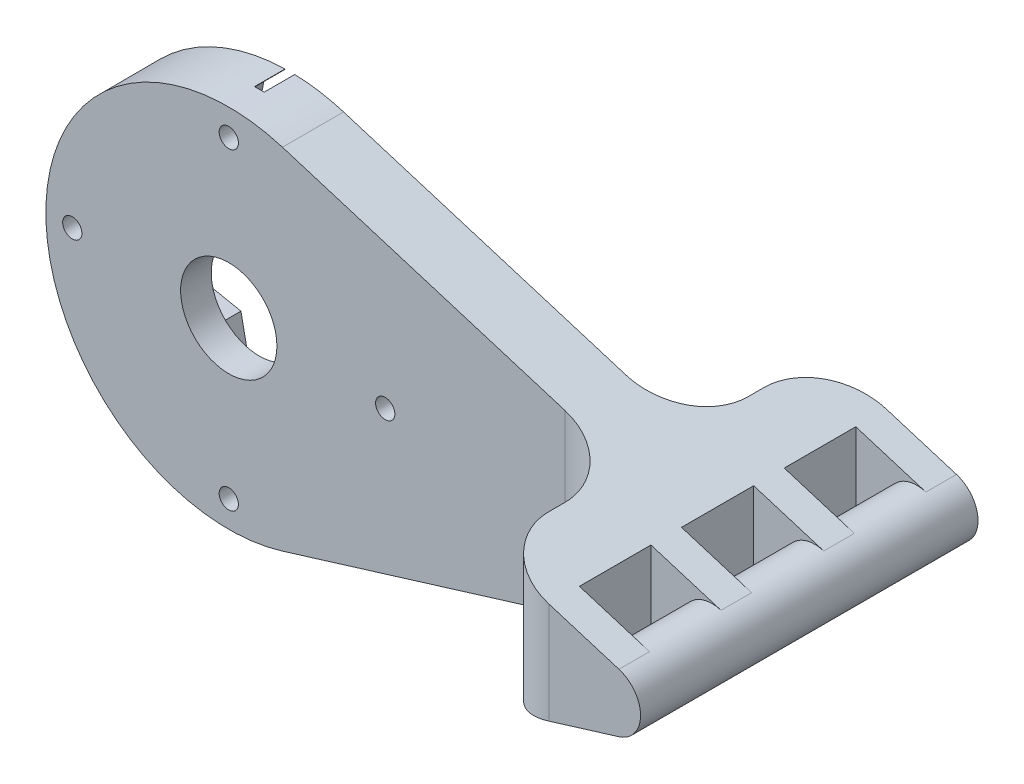
SolidWorks part; units mm, degrees
ref_plane "Front Plane" through (0, 0, 0) normal (0, 0, 1) x (1, 0, 0)
ref_plane "Top Plane" through (0, 0, 0) normal (0, 1, 0) x (1, 0, 0)
ref_plane "Right Plane" through (0, 0, 0) normal (1, 0, 0) x (0, 0, -1)
sketch "Sketch1" plane through (0, 0, 0) normal (0, 0, 1) x (1, 0, 0)
  line L7 (146.05, 3.175) -> (146.05, 4.063)
  line L8 (0, 0) -> (279.4, 0)
  line L9 (0, 0) -> (0, 3.175)
  line L10 (0, 3.175) -> (279.4, 3.175)
  line L11 (279.4, 0) -> (279.4, 3.175)
  line L12 (260.35, 3.175) -> (215.9, 3.175)
  line L13 (260.35, 3.175) -> (260.35, 91.44) construction
  line L14 (254, 97.79) -> (222.25, 97.79)
  line L15 (215.9, 3.175) -> (215.9, 91.44) construction
  line L16 (260.35, 91.44) -> (279.4, 3.175)
  line L17 (165.0718, 64.0362) -> (215.9, 13.208) construction
  line L18 (170.5184, 69.8101) -> (222.7846, 20.5062)
  line L19 (215.9, 91.44) -> (215.9, 89.5783)
  line L20 (0, 19.05) -> (0, 30.1625)
  line L21 (3.175, 19.05) -> (3.175, 30.1625)
  line L22 (3.175, 30.1625) -> (0, 30.1625) construction
  line L23 (26.8735, 12.7) -> (70.8676, 19.05)
  line L24 (238.125, 97.79) -> (238.125, 3.175) construction
  line L25 (165.0718, 64.0362) -> (292.0718, 64.0362) construction
  line L26 (238.125, 76.7362) -> (292.0718, 67.2112)
  line L27 (238.125, 51.3362) -> (292.0718, 60.8612)
  arc A6 (260.35, 91.44) -> (254, 97.79) centre (254, 91.44) ccw
  arc A7 (222.25, 97.79) -> (215.9, 91.44) centre (222.25, 91.44) ccw
  circle A9 centre (215.9, 13.208) radius 3.175
  arc A10 (216.7962, 82.0441) -> (216.9572, 88.0838) centre (215.9, 85.09) ccw
  arc A11 (154.4343, 15.0798) -> (215.6899, 80.8367) centre (131.5684, 97.79) ccw
  arc A12 (146.05, 4.063) -> (154.4343, 15.0798) centre (157.48, 4.063) cw
  circle A13 centre (215.9, 13.208) radius 10.033
  circle A14 centre (165.0718, 64.0362) radius 3.175
  circle A15 centre (165.0718, 64.0362) radius 7.9375
  arc A16 (0, 19.05) -> (15.875, 3.175) centre (15.875, 19.05) ccw
  arc A17 (3.175, 19.05) -> (26.8735, 12.7) centre (15.875, 19.05) ccw
  circle A18 centre (15.875, 19.05) radius 15.875 construction
  circle A19 centre (15.875, 19.05) radius 12.7 construction
  arc A20 (70.8676, 19.05) -> (158.9067, 69.0358) centre (51.0253, 156.5215) ccw
  arc A21 (215.6899, 80.8367) -> (216.7962, 82.0441) centre (217.2436, 80.5236) cw
  arc A22 (215.9, 89.5783) -> (216.9572, 88.0838) centre (217.485, 89.5783) ccw
  arc A23 (3.175, 30.1625) -> (0, 30.1625) centre (1.5875, 30.1625) ccw
  circle A24 centre (238.125, 64.0362) radius 12.7
  circle A25 centre (292.0718, 64.0362) radius 3.175
  point P11 (260.35, 97.79)
  point P14 (215.9, 97.79)
  point P27 (146.05, 13.208)
  point P48 (215.9, 81.915)
  point P51 (215.9, 88.265)
  dimension "D4" = 97.79
  dimension "D6" = 6.35
  dimension "D8" = 6.35
  dimension "D7" = 6.35
  dimension "D10" = 12.7
  dimension "D12" = 11.43
  dimension "D13" = 6.35
  dimension "D16" = 15.875
  dimension "D18" = 31.75
  dimension "D24" = 1.585
  dimension "D26" = 25.4
  dimension "D27" = 6.35
  dimension "D1" = 3.175
  dimension "D2" = 279.4
  dimension "D3" = 44.45
  dimension "D5" = 19.05
  dimension "D9" = 71.882
  dimension "D11" = 114.3
  dimension "D14" = 71.882
  dimension "D15" = 45
  dimension "D17" = 200.025
  dimension "D19" = 30.1625
  dimension "D21" = 12.7
  dimension "D22" = 44.45
  dimension "D23" = 19.05
  dimension "D25" = 127
  dimension "D20" = 3.175
ref_plane "Plane2" through (0, 0, 17.526) normal (0, 0, 1) x (1, 0, 0)
ref_plane "Plane3" through (0, 0, 34.925) normal (0, 0, 1) x (1, 0, 0)
ref_plane "Plane4" through (0, 0, 22.2885) normal (0, 0, 1) x (1, 0, 0)
sketch "Sketch3" plane through (0, 0, 0) normal (0, 0, 1) x (1, 0, 0)
  line L0 (293.0031, 67.0716) -> (243.6986, 82.2004)
  line L1 (243.6986, 45.8721) -> (293.0031, 61.0009)
  arc A0 (243.6986, 82.2004) -> (243.6986, 45.8721) centre (238.125, 64.0362) ccw
  circle A1 centre (238.125, 64.0362) radius 16.25 construction
  circle A2 centre (238.125, 80.2862) radius 1
  circle A3 centre (254.375, 64.0362) radius 1
  circle A4 centre (221.875, 64.0362) radius 1
  circle A5 centre (238.125, 47.7862) radius 1
  arc A6 (293.0031, 61.0009) -> (293.0031, 67.0716) centre (292.0718, 64.0362) ccw
  point P0 (238.125, 64.0362)
  point P2 (292.0718, 64.0362)
  dimension "D1" = 38
  dimension "D2" = 32.5
  dimension "D3" = 2
  dimension "D4" = 6.35
extrude "Boss-Extrude1" add sketch "Sketch3" along normal blind 3.175
sketch "Sketch4" plane through (0, 0, 0) normal (0, 0, -1) x (-1, 0, 0)
  line L0 (-254.925, 66.7307) -> (-239.325, 69.915)
  line L1 (-254.925, 61.3418) -> (-239.325, 58.1575)
  line L2 (-240.8194, 47.2362) -> (-244.0038, 62.8362)
  line L3 (-240.8194, 80.8362) -> (-244.0038, 65.2362)
  line L4 (-235.4306, 80.8362) -> (-232.2462, 65.2362)
  line L5 (-236.925, 69.915) -> (-221.325, 66.7307)
  line L6 (-235.4306, 47.2362) -> (-232.2462, 62.8362)
  line L7 (-236.925, 58.1575) -> (-221.325, 61.3418)
  line L9 (-238.625, 82.5362) -> (-237.625, 82.5362)
  line L10 (-293.0031, 61.0009) -> (-243.6986, 45.8721)
  line L11 (-243.6986, 82.2004) -> (-293.0031, 67.0716)
  line L12 (-293.0031, 61.0009) -> (-243.6986, 45.8721)
  line L13 (-243.6986, 82.2004) -> (-293.0031, 67.0716)
  line L14 (-238.625, 82.5362) -> (-238.625, 83.5362)
  line L15 (-238.625, 83.5362) -> (-237.625, 83.5362)
  line L16 (-237.625, 82.5362) -> (-237.625, 83.5362)
  line L17 (-238.625, 82.5362) -> (-237.625, 83.5362) construction
  line L18 (-238.625, 83.5362) -> (-237.625, 82.5362) construction
  line L19 (-238.625, 44.5362) -> (-237.625, 44.5362)
  line L20 (-238.625, 44.5362) -> (-238.625, 45.5362)
  line L21 (-238.625, 45.5362) -> (-237.625, 45.5362)
  line L22 (-237.625, 44.5362) -> (-237.625, 45.5362)
  line L23 (-238.625, 44.5362) -> (-237.625, 45.5362) construction
  line L24 (-238.625, 45.5362) -> (-237.625, 44.5362) construction
  line L25 (-219.625, 63.5362) -> (-218.625, 63.5362)
  line L26 (-219.625, 63.5362) -> (-219.625, 64.5362)
  line L27 (-219.625, 64.5362) -> (-218.625, 64.5362)
  line L28 (-218.625, 63.5362) -> (-218.625, 64.5362)
  line L29 (-219.625, 63.5362) -> (-218.625, 64.5362) construction
  line L30 (-219.625, 64.5362) -> (-218.625, 63.5362) construction
  circle A0 centre (-238.125, 64.0362) radius 6
  circle A1 centre (-238.125, 80.2862) radius 2.75
  circle A2 centre (-221.875, 64.0362) radius 2.75
  circle A3 centre (-238.125, 47.7862) radius 2.75
  circle A4 centre (-254.375, 64.0362) radius 2.75
  arc A5 (-243.6986, 45.8721) -> (-243.6986, 82.2004) centre (-238.125, 64.0362) ccw construction
  arc A6 (-243.6986, 45.8721) -> (-243.6986, 82.2004) centre (-238.125, 64.0362) ccw construction
  arc A9 (-293.0031, 67.0716) -> (-293.0031, 61.0009) centre (-292.0718, 64.0362) ccw
  arc A10 (-243.6986, 45.8721) -> (-243.6986, 82.2004) centre (-238.125, 64.0362) ccw
  arc A11 (-293.0031, 67.0716) -> (-293.0031, 61.0009) centre (-292.0718, 64.0362) ccw
  arc A12 (-243.6986, 45.8721) -> (-243.6986, 82.2004) centre (-238.125, 64.0362) ccw
  point P37 (-238.125, 83.0362)
  point P48 (-238.125, 45.0362)
  point P53 (-219.125, 64.0362)
  arc M17 (-293.0031, 67.0716) -> (-293.0031, 61.0009) centre (-292.0718, 64.0362) ccw
  line M18 (-293.0031, 61.0009) -> (-243.6986, 45.8721)
  arc M19 (-243.6986, 45.8721) -> (-243.6986, 82.2004) centre (-238.125, 64.0362) ccw
  line M20 (-243.6986, 82.2004) -> (-293.0031, 67.0716)
  dimension "D1" = 12
  dimension "D3" = 1
  dimension "D4" = 1
  dimension "D2" = 0
extrude "Boss-Extrude3" add sketch "Sketch4" along normal blind 3.175 contours A4 L0 L3 A1 A3 L2 L1 M19 M20 M17 M18 | A2 L27 L16 A1 L4 L5 M19 | A3 L22 L25 A2 L7 L6 M19 region at (262.9971, 64.0362, 0) region at (228.1389, 74.0223, 0) region at (228.1389, 54.0502, 0)
sketch "Sketch5" plane through (0, 0, 0) normal (0, 0, 1) x (1, 0, 0)
  line L0 (285.7218, 64.0362) -> (285.7218, 69.3058)
  line L1 (285.7218, 64.0362) -> (285.7218, 58.7667)
  line L2 (293.0031, 67.0716) -> (243.6986, 82.2004)
  line L3 (243.6986, 45.8721) -> (293.0031, 61.0009)
  line L4 (293.0031, 67.0716) -> (243.6986, 82.2004)
  line L5 (243.6986, 45.8721) -> (293.0031, 61.0009)
  line L6 (279.3718, 56.8182) -> (279.3718, 71.2543)
  circle A0 centre (292.0718, 64.0362) radius 3.175
  arc A1 (293.0031, 61.0009) -> (293.0031, 67.0716) centre (292.0718, 64.0362) ccw construction
  circle A2 centre (292.0718, 64.0362) radius 6.35
  arc A5 (293.0031, 61.0009) -> (293.0031, 67.0716) centre (292.0718, 64.0362) ccw
  arc A6 (243.6986, 82.2004) -> (243.6986, 45.8721) centre (238.125, 64.0362) ccw
  arc A7 (293.0031, 61.0009) -> (293.0031, 67.0716) centre (292.0718, 64.0362) ccw
  arc A8 (243.6986, 82.2004) -> (243.6986, 45.8721) centre (238.125, 64.0362) ccw
  point P19 (285.7218, 61.4015)
  dimension "D3" = 6.35
  dimension "D1" = 3.175
  dimension "D2" = 0
extrude "Boss-Extrude6" add sketch "Sketch5" along normal mid plane 35.052 contours L6 L5 L1 L0 L4 | A0 region at (282.3816, 64.0362, 0) region at (292.0718, 64.0362, 0)
sketch "Sketch6" plane through (0, 0, -17.526) normal (0, 0, -1) x (-1, 0, 0)
  line L0 (-279.3718, 56.8182) -> (-279.3718, 71.2543) construction
  line L1 (-279.3718, 71.2543) -> (-285.7218, 69.3058) construction
  line L2 (-285.7218, 69.3058) -> (-285.7218, 58.7667) construction
  line L3 (-285.7218, 58.7667) -> (-279.3718, 56.8182) construction
  line L4 (-279.3718, 56.8182) -> (-279.3718, 71.2543)
  line L5 (-279.3718, 71.2543) -> (-285.7218, 69.3058)
  line L6 (-285.7218, 69.3058) -> (-285.7218, 58.7667)
  line L7 (-285.7218, 58.7667) -> (-279.3718, 56.8182)
  line L8 (-285.7218, 58.7667) -> (-293.0031, 61.0009)
  line L9 (-293.0031, 67.0716) -> (-285.7218, 69.3058)
  circle A0 centre (-292.0718, 64.0362) radius 3.175 construction
  circle A1 centre (-292.0718, 64.0362) radius 3.175
  line M2 (-279.3718, 56.8182) -> (-279.3718, 71.2543)
  line M3 (-279.3718, 71.2543) -> (-285.7218, 69.3058)
  line M4 (-285.7218, 69.3058) -> (-285.7218, 58.7667)
  line M5 (-285.7218, 58.7667) -> (-279.3718, 56.8182)
extrude "Boss-Extrude7" add sketch "Sketch6" against normal blind 3.175 contours A1 L8 L9 M4 | A1 | M5 M2 M3 M4 region at (282.3816, 64.0362, -17.526) region at (287.8218, 64.0362, -17.526) region at (292.0718, 64.0362, -17.526)
sketch "Sketch7" plane through (0, 0, 3.175) normal (0, 0, 1) x (1, 0, 0)
  line L3 (285.7218, 58.7667) -> (293.0031, 61.0009)
  line L4 (293.0031, 67.0716) -> (285.7218, 69.3058)
  line L5 (285.7218, 69.3058) -> (285.7218, 58.7667)
  line L6 (285.7218, 58.7667) -> (293.0031, 61.0009)
  line L7 (293.0031, 67.0716) -> (285.7218, 69.3058)
  line L8 (285.7218, 69.3058) -> (285.7218, 58.7667)
  arc A1 (293.0031, 67.0716) -> (293.0031, 61.0009) centre (292.0718, 64.0362) ccw
  arc A2 (293.0031, 67.0716) -> (293.0031, 61.0009) centre (292.0718, 64.0362) ccw
  dimension "D1" = 0
extrude "Cut-Extrude1" cut sketch "Sketch7" against normal up to next
ref_plane "Plane5" through (0, 0, -5.334) normal (0, 0, 1) x (1, 0, 0)
extrude "Boss-Extrude8" add sketch "Sketch7<5>" along normal mid plane 3.175 from surface starting at plane "Plane5"
sketch "Sketch7<5>" plane through (0, 0, 3.175) normal (0, 0, 1) x (1, 0, 0) same geometry as "Sketch7"
mirror "Mirror3" about plane through (0, 0, 0) normal (0, 0, 1) of "Boss-Extrude7"
ref_plane "Plane6" through (0, 0, 5.334) normal (0, 0, -1) x (-1, 0, 0)
extrude "Boss-Extrude9" add sketch "Sketch7<6>" along normal mid plane 3.175 from surface starting at plane "Plane6"
sketch "Sketch7<6>" plane through (0, 0, 3.175) normal (0, 0, 1) x (1, 0, 0) same geometry as "Sketch7"
fillet "Fillet2" radius 6.35 4 edges at (279.3718, 64.0362, -17.526) (279.3718, 64.0362, -3.175) (279.3718, 64.0362, 17.526) (279.3718, 64.0362, 3.175)
sketch "Sketch8" plane through (0, 0, 3.175) normal (0, 0, 1) x (1, 0, 0)
  arc A0 (243.6986, 82.2004) -> (243.6986, 45.8721) centre (238.125, 64.0362) ccw construction
  arc A1 (243.6986, 82.2004) -> (243.6986, 45.8721) centre (238.125, 64.0362) ccw
  circle A2 centre (238.125, 64.0362) radius 5
  dimension "D1" = 10
extrude "Cut-Extrude2" cut sketch "Sketch8" against normal through all contours A2 region at (238.125, 64.0362, 3.175)
